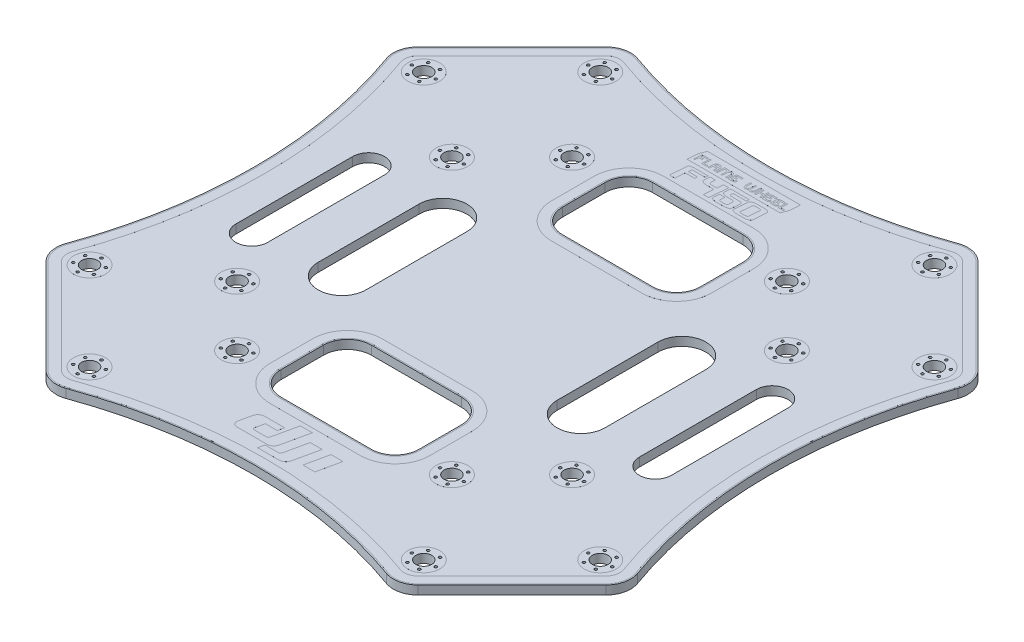
SolidWorks part; units mm, degrees
material "Mounting Plate Material"
ref_plane "Front Plane" through (0, 0, 0) normal (0, 0, 1) x (1, 0, 0)
ref_plane "Top Plane" through (0, 0, 0) normal (0, 1, 0) x (1, 0, 0)
ref_plane "Right Plane" through (0, 0, 0) normal (1, 0, 0) x (0, 0, -1)
sketch "Sketch1" plane through (0, 0, 0) normal (0, 1, 0) x (1, 0, 0)
  line L0 (-48.55, 0) -> (48.55, 0) construction
  line L1 (0, 48.55) -> (0, -48.55) construction
  line L2 (-30.1605, 53.8) -> (30.1605, 53.8) construction
  line L3 (0, 48.55) -> (0, 53.8) construction
  line L4 (-53.8, 30.1605) -> (-53.8, -30.1605) construction
  line L5 (-30.1605, -53.8) -> (30.1605, -53.8) construction
  line L6 (53.8, -30.1605) -> (53.8, 30.1605) construction
  line L7 (35.0464, 52.7056) -> (52.7056, 35.0464)
  line L8 (-52.7056, 35.0464) -> (-35.0464, 52.7056)
  line L9 (-52.7056, -35.0464) -> (-35.0464, -52.7056)
  line L10 (35.0464, -52.7056) -> (52.7056, -35.0464)
  line L11 (-43.876, -43.876) -> (43.876, 43.876) construction
  line L12 (-43.876, 43.876) -> (43.876, -43.876) construction
  line L13 (-31.7403, 54.075) -> (-31.7403, -54.075) construction
  line L14 (-31.7403, -54.075) -> (31.7403, -54.075) construction
  arc A0 (-30.1605, 53.8) -> (30.1605, 53.8) centre (0, 137.8088) ccw
  arc A1 (53.8, 30.1605) -> (53.8, -30.1605) centre (137.8088, 0) ccw
  arc A2 (30.1605, -53.8) -> (-30.1605, -53.8) centre (0, -137.8088) ccw
  arc A3 (-53.8, -30.1605) -> (-53.8, 30.1605) centre (-137.8088, 0) ccw
  arc A4 (-53.8, -30.1605) -> (-52.7056, -35.0464) centre (-49.3995, -31.7403) ccw
  arc A5 (-35.0464, -52.7056) -> (-30.1605, -53.8) centre (-31.7403, -49.3995) ccw
  arc A6 (30.1605, -53.8) -> (35.0464, -52.7056) centre (31.7403, -49.3995) ccw
  arc A7 (52.7056, -35.0464) -> (53.8, -30.1605) centre (49.3995, -31.7403) ccw
  arc A8 (53.8, 30.1605) -> (52.7056, 35.0464) centre (49.3995, 31.7403) ccw
  arc A9 (35.0464, 52.7056) -> (30.1605, 53.8) centre (31.7403, 49.3995) ccw
  arc A10 (-30.1605, 53.8) -> (-35.0464, 52.7056) centre (-31.7403, 49.3995) ccw
  arc A11 (-52.7056, 35.0464) -> (-53.8, 30.1605) centre (-49.3995, 31.7403) ccw
  point P2 (0, 0)
  point P6 (0, 0)
  point P34 (0, 0)
  dimension "D2" = 108.15
  dimension "D4" = 124.1
  dimension "D1" = 97.1
  dimension "D3" = 5.25
  dimension "D5" = 45
extrude "Boss-Extrude1" add sketch "Sketch1" along normal blind 0.825 and the other way blind 0.825
sketch "Sketch2" plane through (0, 0.825, 0) normal (0, 1, 0) x (1, 0, 0)
  line L0 (0, 18) -> (0, -18) construction
  line L1 (0, 35) -> (0, 18) construction
  line L2 (0, -18) -> (0, -35) construction
  line L3 (-13, 26.5) -> (13, 26.5) construction
  line L4 (13, 30.5) -> (13, 22.5)
  line L5 (-13, 30.5) -> (-13, 22.5)
  line L6 (-8.5, 35) -> (8.5, 35)
  line L7 (-8.5, 18) -> (8.5, 18)
  line L8 (-13, -26.5) -> (13, -26.5) construction
  line L9 (-13, -22.5) -> (-13, -30.5)
  line L10 (13, -22.5) -> (13, -30.5)
  line L11 (-8.5, -18) -> (8.5, -18)
  line L12 (-8.5, -35) -> (8.5, -35)
  line L13 (-18, 0) -> (18, 0) construction
  line L14 (-18, 0) -> (-27, 0) construction
  line L15 (18, 0) -> (27, 0) construction
  line L16 (-22.5, 9.5) -> (-22.5, -9.5) construction
  line L17 (22.5, 9.5) -> (22.5, -9.5) construction
  line L18 (-27, -9.5) -> (-27, 9.5)
  line L19 (-18, -9.5) -> (-18, 9.5)
  line L20 (18, -9.5) -> (18, 9.5)
  line L21 (27, -9.5) -> (27, 9.5)
  line L22 (-35, 0) -> (-27, 0) construction
  line L23 (-41, 0) -> (-35, 0) construction
  line L24 (27, 0) -> (35, 0) construction
  line L25 (35, 0) -> (41, 0) construction
  line L26 (-35, 11) -> (-35, -11)
  line L27 (-41, 11) -> (-41, -11)
  line L28 (-38, 11) -> (-38, -11) construction
  line L29 (35, 11) -> (35, -11)
  line L30 (41, 11) -> (41, -11)
  line L31 (38, 11) -> (38, -11) construction
  arc A0 (-8.5, 35) -> (-13, 30.5) centre (-8.5, 30.5) ccw
  arc A1 (13, 30.5) -> (8.5, 35) centre (8.5, 30.5) ccw
  arc A2 (-13, 22.5) -> (-8.5, 18) centre (-8.5, 22.5) ccw
  arc A3 (8.5, 18) -> (13, 22.5) centre (8.5, 22.5) ccw
  arc A4 (-8.5, -18) -> (-13, -22.5) centre (-8.5, -22.5) ccw
  arc A5 (13, -22.5) -> (8.5, -18) centre (8.5, -22.5) ccw
  arc A6 (8.5, -35) -> (13, -30.5) centre (8.5, -30.5) ccw
  arc A7 (-13, -30.5) -> (-8.5, -35) centre (-8.5, -30.5) ccw
  arc A8 (27, 9.5) -> (18, 9.5) centre (22.5, 9.5) ccw
  arc A9 (18, -9.5) -> (27, -9.5) centre (22.5, -9.5) ccw
  arc A10 (-27, -9.5) -> (-18, -9.5) centre (-22.5, -9.5) ccw
  arc A11 (-18, 9.5) -> (-27, 9.5) centre (-22.5, 9.5) ccw
  arc A12 (-35, 11) -> (-41, 11) centre (-38, 11) ccw
  arc A13 (-41, -11) -> (-35, -11) centre (-38, -11) ccw
  arc A14 (41, 11) -> (35, 11) centre (38, 11) ccw
  arc A15 (35, -11) -> (41, -11) centre (38, -11) ccw
  point P5 (0, 26.5)
  point P22 (0, -26.5)
  point P34 (-22.5, 0)
  point P36 (0, 0)
  point P45 (22.5, 0)
  point P64 (-38, 0)
  point P69 (38, 0)
  dimension "D6" = 26
  dimension "D8" = 36
  dimension "D13" = 8
  dimension "D18" = 22
  dimension "D1" = 36
  dimension "D2" = 17
  dimension "D3" = 17
  dimension "D4" = 26
  dimension "D5" = 8
  dimension "D7" = 8
  dimension "D9" = 9
  dimension "D10" = 9
  dimension "D11" = 19
  dimension "D12" = 19
  dimension "D14" = 8
  dimension "D15" = 6
  dimension "D16" = 6
  dimension "D17" = 22
extrude "Cut-Extrude1" cut sketch "Sketch2" against normal up to surface (1.65 mm away) up to face at (0, -0.825, 0)
sketch "Sketch3" plane through (0, 0.825, 0) normal (0, 1, 0) x (1, 0, 0)
  line L0 (-48.0833, -31.4663) -> (-31.4663, -48.0833) construction
  line L1 (-52.7056, -35.0464) -> (-35.0464, -52.7056) construction
  line L2 (-39.7748, -39.7748) -> (-43.876, -43.876) construction
  line L3 (43.876, -43.876) -> (39.7748, -39.7748) construction
  line L4 (31.4663, -48.0833) -> (48.0833, -31.4663) construction
  line L5 (43.876, 43.876) -> (39.7748, 39.7748) construction
  line L6 (31.4663, 48.0833) -> (48.0833, 31.4663) construction
  line L7 (-43.876, 43.876) -> (-39.7748, 39.7748) construction
  line L8 (-31.4663, 48.0833) -> (-48.0833, 31.4663) construction
  line L9 (-35.0464, 52.7056) -> (-52.7056, 35.0464) construction
  line L10 (52.7056, 35.0464) -> (35.0464, 52.7056) construction
  line L11 (35.0464, -52.7056) -> (52.7056, -35.0464) construction
  line L12 (-31.5403, -20.2266) -> (-20.2266, -31.5403) construction
  line L13 (31.5403, -20.2266) -> (20.2266, -31.5403) construction
  line L14 (-31.5403, 20.2266) -> (-20.2266, 31.5403) construction
  line L15 (20.2266, 31.5403) -> (31.5403, 20.2266) construction
  line L16 (-25.8834, -25.8834) -> (-39.7748, -39.7748) construction
  line L17 (-39.7748, 39.7748) -> (-25.8834, 25.8834) construction
  line L18 (39.7748, 39.7748) -> (25.8834, 25.8834) construction
  line L19 (25.8834, -25.8834) -> (39.7748, -39.7748) construction
  line L20 (-20.2266, -31.5403) -> (-31.4663, -48.0833) construction
  line L21 (-31.5403, -20.2266) -> (-48.0833, -31.4663) construction
  circle A0 centre (-48.0833, -31.4663) radius 1.5
  circle A1 centre (-31.4663, -48.0833) radius 1.5
  circle A2 centre (31.4663, -48.0833) radius 1.5
  circle A3 centre (48.0833, -31.4663) radius 1.5
  circle A4 centre (48.0833, 31.4663) radius 1.5
  circle A5 centre (31.4663, 48.0833) radius 1.5
  circle A6 centre (-31.4663, 48.0833) radius 1.5
  circle A7 centre (-48.0833, 31.4663) radius 1.5
  circle A8 centre (-31.5403, -20.2266) radius 1.5
  circle A9 centre (-20.2266, -31.5403) radius 1.5
  circle A10 centre (-31.5403, 20.2266) radius 1.5
  circle A11 centre (-20.2266, 31.5403) radius 1.5
  circle A12 centre (20.2266, 31.5403) radius 1.5
  circle A13 centre (31.5403, 20.2266) radius 1.5
  circle A14 centre (31.5403, -20.2266) radius 1.5
  circle A15 centre (20.2266, -31.5403) radius 1.5
  dimension "D3" = 3
  dimension "D4" = 20
  dimension "D1" = 23.5
  dimension "D2" = 5.8
  dimension "D5" = 16
extrude "Cut-Extrude2" cut sketch "Sketch3" against normal up to surface (1.65 mm away) up to face at (38, -0.825, 0)
sketch "Sketch4" plane through (0, 0.825, 0) normal (0, 1, 0) x (1, 0, 0)
  line L0 (13.25, -30.5) -> (13.25, -22.5)
  line L1 (-13.25, -30.5) -> (-13.25, -22.5)
  line L2 (-8.5, -17.75) -> (8.5, -17.75)
  line L3 (-8.5, -35.25) -> (8.5, -35.25)
  line L4 (13, -30.5) -> (13, -22.5) construction
  line L5 (15.05, -30.5) -> (15.05, -22.5)
  line L6 (-8.5, -15.95) -> (8.5, -15.95)
  line L7 (-15.05, -30.5) -> (-15.05, -22.5)
  line L8 (-8.5, -37.05) -> (8.5, -37.05)
  line L9 (-8.5, 17.75) -> (8.5, 17.75)
  line L10 (-13.25, 22.5) -> (-13.25, 30.5)
  line L11 (-8.5, 35.25) -> (8.5, 35.25)
  line L12 (13.25, 30.5) -> (13.25, 22.5)
  line L13 (13, 22.5) -> (13, 30.5) construction
  line L14 (15.05, 30.5) -> (15.05, 22.5)
  line L15 (-8.5, 15.95) -> (8.5, 15.95)
  line L16 (-15.05, 22.5) -> (-15.05, 30.5)
  line L17 (-8.5, 37.05) -> (8.5, 37.05)
  line L18 (34.8696, -52.5288) -> (52.5288, -34.8696)
  line L19 (35.0464, -52.7056) -> (52.7056, -35.0464) construction
  line L20 (34.8696, 52.5288) -> (52.5288, 34.8696)
  line L21 (52.7056, 35.0464) -> (35.0464, 52.7056) construction
  line L22 (-52.5288, 34.8696) -> (-34.8696, 52.5288)
  line L23 (-35.0464, 52.7056) -> (-52.7056, 35.0464) construction
  line L24 (-52.5288, -34.8696) -> (-34.8696, -52.5288)
  line L25 (-52.7056, -35.0464) -> (-35.0464, -52.7056) construction
  line L26 (-51.256, 33.5968) -> (-33.5968, 51.256)
  line L27 (33.5968, 51.256) -> (51.256, 33.5968)
  line L28 (33.5968, -51.256) -> (51.256, -33.5968)
  line L29 (-51.256, -33.5968) -> (-33.5968, -51.256)
  line L30 (-31.4663, -45.8333) -> (-31.4663, -46.5833) construction
  line L31 (-29.5177, -46.9583) -> (-31.4663, -45.8333) construction
  line L32 (-31.4663, -45.8333) -> (-33.4148, -46.9583) construction
  line L33 (-33.4148, -46.9583) -> (-33.4148, -49.2083) construction
  line L34 (-33.4148, -49.2083) -> (-31.4663, -50.3333) construction
  line L35 (-31.4663, -50.3333) -> (-29.5177, -49.2083) construction
  line L36 (-29.5177, -49.2083) -> (-29.5177, -46.9583) construction
  line L37 (-31.4663, -45.8333) -> (-31.4663, -45.0833) construction
  line L39 (-48.0833, -29.2163) -> (-50.0318, -30.3413) construction
  line L40 (-50.0318, -30.3413) -> (-50.0318, -32.5913) construction
  line L41 (-50.0318, -32.5913) -> (-48.0833, -33.7163) construction
  line L42 (-48.0833, -33.7163) -> (-46.1347, -32.5913) construction
  line L43 (-46.1347, -32.5913) -> (-46.1347, -30.3413) construction
  line L44 (-46.1347, -30.3413) -> (-48.0833, -29.2163) construction
  line L45 (-31.5403, -17.9766) -> (-33.4888, -19.1016) construction
  line L46 (-33.4888, -19.1016) -> (-33.4888, -21.3516) construction
  line L47 (-33.4888, -21.3516) -> (-31.5403, -22.4766) construction
  line L48 (-31.5403, -22.4766) -> (-29.5917, -21.3516) construction
  line L49 (-29.5917, -21.3516) -> (-29.5917, -19.1016) construction
  line L50 (-29.5917, -19.1016) -> (-31.5403, -17.9766) construction
  line L51 (-20.2266, -29.2903) -> (-22.1751, -30.4153) construction
  line L52 (-22.1751, -30.4153) -> (-22.1751, -32.6653) construction
  line L53 (-22.1751, -32.6653) -> (-20.2266, -33.7903) construction
  line L54 (-20.2266, -33.7903) -> (-18.278, -32.6653) construction
  line L55 (-18.278, -32.6653) -> (-18.278, -30.4153) construction
  line L56 (-18.278, -30.4153) -> (-20.2266, -29.2903) construction
  line L57 (20.2266, 33.7903) -> (18.278, 32.6653) construction
  line L58 (18.278, 32.6653) -> (18.278, 30.4153) construction
  line L59 (18.278, 30.4153) -> (20.2266, 29.2903) construction
  line L60 (20.2266, 29.2903) -> (22.1751, 30.4153) construction
  line L61 (22.1751, 30.4153) -> (22.1751, 32.6653) construction
  line L62 (22.1751, 32.6653) -> (20.2266, 33.7903) construction
  line L63 (31.5403, 22.4766) -> (29.5917, 21.3516) construction
  line L64 (29.5917, 21.3516) -> (29.5917, 19.1016) construction
  line L65 (29.5917, 19.1016) -> (31.5403, 17.9766) construction
  line L66 (31.5403, 17.9766) -> (33.4888, 19.1016) construction
  line L67 (33.4888, 19.1016) -> (33.4888, 21.3516) construction
  line L68 (33.4888, 21.3516) -> (31.5403, 22.4766) construction
  line L69 (48.0833, 33.7163) -> (46.1347, 32.5913) construction
  line L70 (46.1347, 32.5913) -> (46.1347, 30.3413) construction
  line L71 (46.1347, 30.3413) -> (48.0833, 29.2163) construction
  line L72 (48.0833, 29.2163) -> (50.0318, 30.3413) construction
  line L73 (50.0318, 30.3413) -> (50.0318, 32.5913) construction
  line L74 (50.0318, 32.5913) -> (48.0833, 33.7163) construction
  line L75 (31.4663, 50.3333) -> (29.5177, 49.2083) construction
  line L76 (29.5177, 49.2083) -> (29.5177, 46.9583) construction
  line L77 (29.5177, 46.9583) -> (31.4663, 45.8333) construction
  line L78 (31.4663, 45.8333) -> (33.4148, 46.9583) construction
  line L79 (33.4148, 46.9583) -> (33.4148, 49.2083) construction
  line L80 (33.4148, 49.2083) -> (31.4663, 50.3333) construction
  line L81 (-50.3333, 31.4663) -> (-49.2083, 29.5177) construction
  line L82 (-49.2083, 29.5177) -> (-46.9583, 29.5177) construction
  line L83 (-46.9583, 29.5177) -> (-45.8333, 31.4663) construction
  line L84 (-45.8333, 31.4663) -> (-46.9583, 33.4148) construction
  line L85 (-46.9583, 33.4148) -> (-49.2083, 33.4148) construction
  line L86 (-49.2083, 33.4148) -> (-50.3333, 31.4663) construction
  line L87 (-33.7903, 20.2266) -> (-32.6653, 18.278) construction
  line L88 (-32.6653, 18.278) -> (-30.4153, 18.278) construction
  line L89 (-30.4153, 18.278) -> (-29.2903, 20.2266) construction
  line L90 (-29.2903, 20.2266) -> (-30.4153, 22.1751) construction
  line L91 (-30.4153, 22.1751) -> (-32.6653, 22.1751) construction
  line L92 (-32.6653, 22.1751) -> (-33.7903, 20.2266) construction
  line L93 (-22.4766, 31.5403) -> (-21.3516, 29.5917) construction
  line L94 (-21.3516, 29.5917) -> (-19.1016, 29.5917) construction
  line L95 (-19.1016, 29.5917) -> (-17.9766, 31.5403) construction
  line L96 (-17.9766, 31.5403) -> (-19.1016, 33.4888) construction
  line L97 (-19.1016, 33.4888) -> (-21.3516, 33.4888) construction
  line L98 (-21.3516, 33.4888) -> (-22.4766, 31.5403) construction
  line L99 (-29.2163, 48.0833) -> (-30.3413, 50.0318) construction
  line L100 (-30.3413, 50.0318) -> (-32.5913, 50.0318) construction
  line L101 (-32.5913, 50.0318) -> (-33.7163, 48.0833) construction
  line L102 (-33.7163, 48.0833) -> (-32.5913, 46.1347) construction
  line L103 (-32.5913, 46.1347) -> (-30.3413, 46.1347) construction
  line L104 (-30.3413, 46.1347) -> (-29.2163, 48.0833) construction
  line L105 (22.4766, -31.5403) -> (21.3516, -29.5917) construction
  line L106 (21.3516, -29.5917) -> (19.1016, -29.5917) construction
  line L107 (19.1016, -29.5917) -> (17.9766, -31.5403) construction
  line L108 (17.9766, -31.5403) -> (19.1016, -33.4888) construction
  line L109 (19.1016, -33.4888) -> (21.3516, -33.4888) construction
  line L110 (21.3516, -33.4888) -> (22.4766, -31.5403) construction
  line L111 (33.7903, -20.2266) -> (32.6653, -18.278) construction
  line L112 (32.6653, -18.278) -> (30.4153, -18.278) construction
  line L113 (30.4153, -18.278) -> (29.2903, -20.2266) construction
  line L114 (29.2903, -20.2266) -> (30.4153, -22.1751) construction
  line L115 (30.4153, -22.1751) -> (32.6653, -22.1751) construction
  line L116 (32.6653, -22.1751) -> (33.7903, -20.2266) construction
  line L117 (33.7163, -48.0833) -> (32.5913, -46.1347) construction
  line L118 (32.5913, -46.1347) -> (30.3413, -46.1347) construction
  line L119 (30.3413, -46.1347) -> (29.2163, -48.0833) construction
  line L120 (29.2163, -48.0833) -> (30.3413, -50.0318) construction
  line L121 (30.3413, -50.0318) -> (32.5913, -50.0318) construction
  line L122 (32.5913, -50.0318) -> (33.7163, -48.0833) construction
  line L123 (50.3333, -31.4663) -> (49.2083, -29.5177) construction
  line L124 (49.2083, -29.5177) -> (46.9583, -29.5177) construction
  line L125 (46.9583, -29.5177) -> (45.8333, -31.4663) construction
  line L126 (45.8333, -31.4663) -> (46.9583, -33.4148) construction
  line L127 (46.9583, -33.4148) -> (49.2083, -33.4148) construction
  line L128 (49.2083, -33.4148) -> (50.3333, -31.4663) construction
  arc A0 (-8.5, -17.75) -> (-13.25, -22.5) centre (-8.5, -22.5) ccw
  arc A1 (13.25, -22.5) -> (8.5, -17.75) centre (8.5, -22.5) ccw
  arc A2 (-13.25, -30.5) -> (-8.5, -35.25) centre (-8.5, -30.5) ccw
  arc A3 (8.5, -35.25) -> (13.25, -30.5) centre (8.5, -30.5) ccw
  arc A4 (8.5, -35) -> (13, -30.5) centre (8.5, -30.5) ccw construction
  arc A5 (13, -22.5) -> (8.5, -18) centre (8.5, -22.5) ccw construction
  arc A6 (-8.5, -18) -> (-13, -22.5) centre (-8.5, -22.5) ccw construction
  arc A7 (-13, -30.5) -> (-8.5, -35) centre (-8.5, -30.5) ccw construction
  arc A8 (15.05, -22.5) -> (8.5, -15.95) centre (8.5, -22.5) ccw
  arc A9 (-8.5, -15.95) -> (-15.05, -22.5) centre (-8.5, -22.5) ccw
  arc A10 (-15.05, -30.5) -> (-8.5, -37.05) centre (-8.5, -30.5) ccw
  arc A11 (8.5, -37.05) -> (15.05, -30.5) centre (8.5, -30.5) ccw
  arc A12 (-13.25, 22.5) -> (-8.5, 17.75) centre (-8.5, 22.5) ccw
  arc A13 (-8.5, 35.25) -> (-13.25, 30.5) centre (-8.5, 30.5) ccw
  arc A14 (13.25, 30.5) -> (8.5, 35.25) centre (8.5, 30.5) ccw
  arc A15 (8.5, 17.75) -> (13.25, 22.5) centre (8.5, 22.5) ccw
  arc A16 (8.5, 18) -> (13, 22.5) centre (8.5, 22.5) ccw construction
  arc A17 (13, 30.5) -> (8.5, 35) centre (8.5, 30.5) ccw construction
  arc A18 (-8.5, 35) -> (-13, 30.5) centre (-8.5, 30.5) ccw construction
  arc A19 (-13, 22.5) -> (-8.5, 18) centre (-8.5, 22.5) ccw construction
  arc A20 (8.5, 15.95) -> (15.05, 22.5) centre (8.5, 22.5) ccw
  arc A21 (-15.05, 22.5) -> (-8.5, 15.95) centre (-8.5, 22.5) ccw
  arc A22 (-8.5, 37.05) -> (-15.05, 30.5) centre (-8.5, 30.5) ccw
  arc A23 (15.05, 30.5) -> (8.5, 37.05) centre (8.5, 30.5) ccw
  arc A24 (30.245, -53.5647) -> (-30.245, -53.5647) centre (0, -137.8088) ccw
  arc A25 (30.1605, -53.8) -> (-30.1605, -53.8) centre (0, -137.8088) ccw construction
  arc A26 (-53.5647, -30.245) -> (-53.5647, 30.245) centre (-137.8088, 0) ccw
  arc A27 (-30.245, 53.5647) -> (30.245, 53.5647) centre (0, 137.8088) ccw
  arc A28 (53.5647, 30.245) -> (53.5647, -30.245) centre (137.8088, 0) ccw
  arc A29 (53.8, 30.1605) -> (53.8, -30.1605) centre (137.8088, 0) ccw construction
  arc A30 (-30.1605, 53.8) -> (30.1605, 53.8) centre (0, 137.8088) ccw construction
  arc A31 (-53.8, -30.1605) -> (-53.8, 30.1605) centre (-137.8088, 0) ccw construction
  arc A32 (34.8696, 52.5288) -> (30.245, 53.5647) centre (31.7403, 49.3995) ccw
  arc A33 (35.0464, 52.7056) -> (30.1605, 53.8) centre (31.7403, 49.3995) ccw construction
  arc A34 (53.5647, 30.245) -> (52.5288, 34.8696) centre (49.3995, 31.7403) ccw
  arc A35 (53.8, 30.1605) -> (52.7056, 35.0464) centre (49.3995, 31.7403) ccw construction
  arc A36 (52.5288, -34.8696) -> (53.5647, -30.245) centre (49.3995, -31.7403) ccw
  arc A37 (52.7056, -35.0464) -> (53.8, -30.1605) centre (49.3995, -31.7403) ccw construction
  arc A38 (30.245, -53.5647) -> (34.8696, -52.5288) centre (31.7403, -49.3995) ccw
  arc A39 (30.1605, -53.8) -> (35.0464, -52.7056) centre (31.7403, -49.3995) ccw construction
  arc A40 (-34.8696, -52.5288) -> (-30.245, -53.5647) centre (-31.7403, -49.3995) ccw
  arc A41 (-35.0464, -52.7056) -> (-30.1605, -53.8) centre (-31.7403, -49.3995) ccw construction
  arc A42 (-53.5647, -30.245) -> (-52.5288, -34.8696) centre (-49.3995, -31.7403) ccw
  arc A43 (-53.8, -30.1605) -> (-52.7056, -35.0464) centre (-49.3995, -31.7403) ccw construction
  arc A44 (-52.5288, 34.8696) -> (-53.5647, 30.245) centre (-49.3995, 31.7403) ccw
  arc A45 (-52.7056, 35.0464) -> (-53.8, 30.1605) centre (-49.3995, 31.7403) ccw construction
  arc A46 (-30.245, 53.5647) -> (-34.8696, 52.5288) centre (-31.7403, 49.3995) ccw
  arc A47 (-30.1605, 53.8) -> (-35.0464, 52.7056) centre (-31.7403, 49.3995) ccw construction
  arc A48 (-51.8706, -30.8532) -> (-51.8706, 30.8532) centre (-137.8088, 0) ccw
  arc A49 (-51.256, 33.5968) -> (-51.8706, 30.8532) centre (-49.3995, 31.7403) ccw
  arc A50 (-30.8532, 51.8706) -> (-33.5968, 51.256) centre (-31.7403, 49.3995) ccw
  arc A51 (-30.8532, 51.8706) -> (30.8532, 51.8706) centre (0, 137.8088) ccw
  arc A52 (33.5968, 51.256) -> (30.8532, 51.8706) centre (31.7403, 49.3995) ccw
  arc A53 (51.8706, 30.8532) -> (51.256, 33.5968) centre (49.3995, 31.7403) ccw
  arc A54 (51.8706, 30.8532) -> (51.8706, -30.8532) centre (137.8088, 0) ccw
  arc A55 (51.256, -33.5968) -> (51.8706, -30.8532) centre (49.3995, -31.7403) ccw
  arc A56 (30.8532, -51.8706) -> (33.5968, -51.256) centre (31.7403, -49.3995) ccw
  arc A57 (30.8532, -51.8706) -> (-30.8532, -51.8706) centre (0, -137.8088) ccw
  arc A58 (-33.5968, -51.256) -> (-30.8532, -51.8706) centre (-31.7403, -49.3995) ccw
  arc A59 (-51.8706, -30.8532) -> (-51.256, -33.5968) centre (-49.3995, -31.7403) ccw
  circle A60 centre (-31.4663, -48.0833) radius 3
  circle A61 centre (-48.0833, -31.4663) radius 3
  circle A62 centre (-31.5403, -20.2266) radius 3
  circle A63 centre (-20.2266, -31.5403) radius 3
  circle A64 centre (-48.0833, 31.4663) radius 3
  circle A65 centre (-31.5403, 20.2266) radius 3
  circle A66 centre (-20.2266, 31.5403) radius 3
  circle A67 centre (-31.4663, 48.0833) radius 3
  circle A68 centre (20.2266, 31.5403) radius 3
  circle A69 centre (31.4663, 48.0833) radius 3
  circle A70 centre (48.0833, 31.4663) radius 3
  circle A71 centre (31.5403, 20.2266) radius 3
  circle A72 centre (20.2266, -31.5403) radius 3
  circle A73 centre (31.5403, -20.2266) radius 3
  circle A74 centre (48.0833, -31.4663) radius 3
  circle A75 centre (31.4663, -48.0833) radius 3
  circle A76 centre (-31.4663, -48.0833) radius 1.5 construction
  circle A77 centre (-48.0833, -31.4663) radius 1.5 construction
  circle A78 centre (-31.5403, -20.2266) radius 1.5 construction
  circle A79 centre (-20.2266, -31.5403) radius 1.5 construction
  circle A80 centre (20.2266, -31.5403) radius 1.5 construction
  circle A81 centre (31.4663, -48.0833) radius 1.5 construction
  circle A82 centre (48.0833, -31.4663) radius 1.5 construction
  circle A83 centre (31.5403, -20.2266) radius 1.5 construction
  circle A84 centre (48.0833, 31.4663) radius 1.5 construction
  circle A85 centre (31.5403, 20.2266) radius 1.5 construction
  circle A86 centre (20.2266, 31.5403) radius 1.5 construction
  circle A87 centre (31.4663, 48.0833) radius 1.5 construction
  circle A88 centre (-20.2266, 31.5403) radius 1.5 construction
  circle A89 centre (-31.5403, 20.2266) radius 1.5 construction
  circle A90 centre (-48.0833, 31.4663) radius 1.5 construction
  circle A91 centre (-31.4663, 48.0833) radius 1.5 construction
  circle A92 centre (-48.0833, -31.4663) radius 1.5
  circle A93 centre (-31.4663, -48.0833) radius 1.5
  circle A94 centre (-20.2266, -31.5403) radius 1.5
  circle A95 centre (-31.5403, -20.2266) radius 1.5
  circle A96 centre (-48.0833, 31.4663) radius 1.5
  circle A97 centre (-31.5403, 20.2266) radius 1.5
  circle A98 centre (-20.2266, 31.5403) radius 1.5
  circle A99 centre (-31.4663, 48.0833) radius 1.5
  circle A100 centre (20.2266, 31.5403) radius 1.5
  circle A101 centre (31.4663, 48.0833) radius 1.5
  circle A102 centre (48.0833, 31.4663) radius 1.5
  circle A103 centre (31.5403, 20.2266) radius 1.5
  circle A104 centre (31.5403, -20.2266) radius 1.5
  circle A105 centre (20.2266, -31.5403) radius 1.5
  circle A106 centre (48.0833, -31.4663) radius 1.5
  circle A107 centre (31.4663, -48.0833) radius 1.5
  circle A108 centre (-31.4663, -48.0833) radius 1.9486 construction
  circle A109 centre (-48.0833, -31.4663) radius 1.9486 construction
  circle A110 centre (-31.5403, -20.2266) radius 1.9486 construction
  circle A111 centre (-20.2266, -31.5403) radius 1.9486 construction
  circle A112 centre (-31.4663, -50.3333) radius 0.25
  circle A113 centre (-29.5177, -49.2083) radius 0.25
  circle A114 centre (-29.5177, -46.9583) radius 0.25
  circle A115 centre (-31.4663, -45.8333) radius 0.25
  circle A116 centre (-33.4148, -46.9583) radius 0.25
  circle A117 centre (-33.4148, -49.2083) radius 0.25
  circle A118 centre (-48.0833, -33.7163) radius 0.25
  circle A119 centre (-46.1347, -32.5913) radius 0.25
  circle A120 centre (-46.1347, -30.3413) radius 0.25
  circle A121 centre (-48.0833, -29.2163) radius 0.25
  circle A122 centre (-50.0318, -30.3413) radius 0.25
  circle A123 centre (-50.0318, -32.5913) radius 0.25
  circle A124 centre (-31.5403, -22.4766) radius 0.25
  circle A125 centre (-29.5917, -21.3516) radius 0.25
  circle A126 centre (-29.5917, -19.1016) radius 0.25
  circle A127 centre (-31.5403, -17.9766) radius 0.25
  circle A128 centre (-33.4888, -19.1016) radius 0.25
  circle A129 centre (-33.4888, -21.3516) radius 0.25
  circle A130 centre (-20.2266, -33.7903) radius 0.25
  circle A131 centre (-18.278, -32.6653) radius 0.25
  circle A132 centre (-18.278, -30.4153) radius 0.25
  circle A133 centre (-20.2266, -29.2903) radius 0.25
  circle A134 centre (-22.1751, -30.4153) radius 0.25
  circle A135 centre (-22.1751, -32.6653) radius 0.25
  circle A136 centre (20.2266, 31.5403) radius 1.9486 construction
  circle A137 centre (31.5403, 20.2266) radius 1.9486 construction
  circle A138 centre (48.0833, 31.4663) radius 1.9486 construction
  circle A139 centre (31.4663, 48.0833) radius 1.9486 construction
  circle A140 centre (20.2266, 29.2903) radius 0.25
  circle A141 centre (22.1751, 30.4153) radius 0.25
  circle A142 centre (22.1751, 32.6653) radius 0.25
  circle A143 centre (18.278, 30.4153) radius 0.25
  circle A144 centre (18.278, 32.6653) radius 0.25
  circle A145 centre (20.2266, 33.7903) radius 0.25
  circle A146 centre (31.4663, 45.8333) radius 0.25
  circle A147 centre (29.5177, 46.9583) radius 0.25
  circle A148 centre (29.5177, 49.2083) radius 0.25
  circle A149 centre (31.4663, 50.3333) radius 0.25
  circle A150 centre (33.4148, 49.2083) radius 0.25
  circle A151 centre (33.4148, 46.9583) radius 0.25
  circle A152 centre (29.5917, 21.3516) radius 0.25
  circle A153 centre (29.5917, 19.1016) radius 0.25
  circle A154 centre (31.5403, 17.9766) radius 0.25
  circle A155 centre (33.4888, 19.1016) radius 0.25
  circle A156 centre (33.4888, 21.3516) radius 0.25
  circle A157 centre (31.5403, 22.4766) radius 0.25
  circle A158 centre (48.0833, 29.2163) radius 0.25
  circle A159 centre (46.1347, 30.3413) radius 0.25
  circle A160 centre (50.0318, 30.3413) radius 0.25
  circle A161 centre (50.0318, 32.5913) radius 0.25
  circle A162 centre (48.0833, 33.7163) radius 0.25
  circle A163 centre (46.1347, 32.5913) radius 0.25
  circle A164 centre (-48.0833, 31.4663) radius 1.9486 construction
  circle A165 centre (-31.5403, 20.2266) radius 1.9486 construction
  circle A166 centre (-20.2266, 31.5403) radius 1.9486 construction
  circle A167 centre (-31.4663, 48.0833) radius 1.9486 construction
  circle A168 centre (-46.9583, 29.5177) radius 0.25
  circle A169 centre (-45.8333, 31.4663) radius 0.25
  circle A170 centre (-46.9583, 33.4148) radius 0.25
  circle A171 centre (-49.2083, 33.4148) radius 0.25
  circle A172 centre (-50.3333, 31.4663) radius 0.25
  circle A173 centre (-49.2083, 29.5177) radius 0.25
  circle A174 centre (-32.6653, 18.278) radius 0.25
  circle A175 centre (-33.7903, 20.2266) radius 0.25
  circle A176 centre (-32.6653, 22.1751) radius 0.25
  circle A177 centre (-30.4153, 22.1751) radius 0.25
  circle A178 centre (-29.2903, 20.2266) radius 0.25
  circle A179 centre (-30.4153, 18.278) radius 0.25
  circle A180 centre (-19.1016, 29.5917) radius 0.25
  circle A181 centre (-21.3516, 29.5917) radius 0.25
  circle A182 centre (-22.4766, 31.5403) radius 0.25
  circle A183 centre (-21.3516, 33.4888) radius 0.25
  circle A184 centre (-19.1016, 33.4888) radius 0.25
  circle A185 centre (-17.9766, 31.5403) radius 0.25
  circle A186 centre (-32.5913, 46.1347) radius 0.25
  circle A187 centre (-33.7163, 48.0833) radius 0.25
  circle A188 centre (-32.5913, 50.0318) radius 0.25
  circle A189 centre (-30.3413, 50.0318) radius 0.25
  circle A190 centre (-29.2163, 48.0833) radius 0.25
  circle A191 centre (-30.3413, 46.1347) radius 0.25
  circle A192 centre (20.2266, -31.5403) radius 1.9486 construction
  circle A193 centre (31.5403, -20.2266) radius 1.9486 construction
  circle A194 centre (31.4663, -48.0833) radius 1.9486 construction
  circle A195 centre (48.0833, -31.4663) radius 1.9486 construction
  circle A196 centre (19.1016, -33.4888) radius 0.25
  circle A197 centre (21.3516, -33.4888) radius 0.25
  circle A198 centre (22.4766, -31.5403) radius 0.25
  circle A199 centre (21.3516, -29.5917) radius 0.25
  circle A200 centre (19.1016, -29.5917) radius 0.25
  circle A201 centre (17.9766, -31.5403) radius 0.25
  circle A202 centre (30.3413, -50.0318) radius 0.25
  circle A203 centre (29.2163, -48.0833) radius 0.25
  circle A204 centre (30.3413, -46.1347) radius 0.25
  circle A205 centre (32.5913, -46.1347) radius 0.25
  circle A206 centre (33.7163, -48.0833) radius 0.25
  circle A207 centre (32.5913, -50.0318) radius 0.25
  circle A208 centre (46.9583, -33.4148) radius 0.25
  circle A209 centre (45.8333, -31.4663) radius 0.25
  circle A210 centre (46.9583, -29.5177) radius 0.25
  circle A211 centre (49.2083, -29.5177) radius 0.25
  circle A212 centre (50.3333, -31.4663) radius 0.25
  circle A213 centre (49.2083, -33.4148) radius 0.25
  circle A214 centre (30.4153, -22.1751) radius 0.25
  circle A215 centre (29.2903, -20.2266) radius 0.25
  circle A216 centre (30.4153, -18.278) radius 0.25
  circle A217 centre (32.6653, -18.278) radius 0.25
  circle A218 centre (33.7903, -20.2266) radius 0.25
  circle A219 centre (32.6653, -22.1751) radius 0.25
  dimension "D1" = 0.25
  dimension "D3" = 0.25
  dimension "D5" = 0.25
  dimension "D7" = 6
  dimension "D8" = 0.5
  dimension "D2" = 1.8
  dimension "D4" = 1.8
  dimension "D6" = 1.8
extrude "Boss-Extrude2" add sketch "Sketch4" along normal blind 0.001 contours A27 A46 L22 A44 A26 A42 L24 A40 A24 A38 L18 A36 A28 A34 L20 A32 A59 A48 A49 L26 A50 A51 A52 L27 A53 A54 A55 L28 A56 A57 A58 L29 | L8 A11 L5 A8 L6 A9 L7 A10 A3 L3 A2 L1 A0 L2 A1 L0 | L14 A23 L17 A22 L16 A21 L15 A20 A15 L9 A12 L10 A13 L11 A14 L12 | A61 A92 | A60 A93 | A63 A94 | A62 A95 | A75 A107 | A72 A105 | A73 A104 | A74 A106 | A71 A103 | A70 A102 | A68 A100 | A69 A101 | A64 A96 | A65 A97 | A66 A98 | A67 A99 region at (12.8716, 0.825, 34.8716) region at (14.6824, 0.825, -26.5) region at (32.3749, 0.825, 52.2324) region at (-34.3814, 0.825, 48.0833) region at (-50.9984, 0.825, 31.4663) region at (-34.4554, 0.825, 20.2266) region at (-23.1417, 0.825, 31.5403) region at (-50.9984, 0.825, -31.4663) region at (-34.4554, 0.825, -20.2266) region at (-23.1417, 0.825, -31.5403) region at (-34.3814, 0.825, -48.0833) region at (17.3114, 0.825, -31.5403) region at (28.5511, 0.825, -48.0833) region at (45.1681, 0.825, -31.4663) region at (28.6251, 0.825, -20.2266) region at (17.3114, 0.825, 31.5403) region at (28.6251, 0.825, 20.2266) region at (45.1681, 0.825, 31.4663) region at (28.5511, 0.825, 48.0833)
mirror "Mirror2" about plane through (0, 0, 0) normal (0, 1, 0) of "Boss-Extrude2"
sketch "Sketch5" plane through (0, 0.825, 0) normal (0, 1, 0) x (1, 0, 0)
  circle A0 centre (-31.4663, -45.8333) radius 0.25
  circle A1 centre (-29.5177, -46.9583) radius 0.25
  circle A2 centre (-29.5177, -49.2083) radius 0.25
  circle A3 centre (-31.4663, -50.3333) radius 0.25
  circle A4 centre (-33.4148, -49.2083) radius 0.25
  circle A5 centre (-33.4148, -46.9583) radius 0.25
  circle A6 centre (-48.0833, -33.7163) radius 0.25
  circle A7 centre (-50.0318, -32.5913) radius 0.25
  circle A8 centre (-50.0318, -30.3413) radius 0.25
  circle A9 centre (-48.0833, -29.2163) radius 0.25
  circle A10 centre (-46.1347, -30.3413) radius 0.25
  circle A11 centre (-46.1347, -32.5913) radius 0.25
  circle A12 centre (-33.4888, -21.3516) radius 0.25
  circle A13 centre (-33.4888, -19.1016) radius 0.25
  circle A14 centre (-31.5403, -17.9766) radius 0.25
  circle A15 centre (-29.5917, -19.1016) radius 0.25
  circle A16 centre (-29.5917, -21.3516) radius 0.25
  circle A17 centre (-31.5403, -22.4766) radius 0.25
  circle A18 centre (-22.1751, -30.4153) radius 0.25
  circle A19 centre (-22.1751, -32.6653) radius 0.25
  circle A20 centre (-20.2266, -33.7903) radius 0.25
  circle A21 centre (-18.278, -32.6653) radius 0.25
  circle A22 centre (-18.278, -30.4153) radius 0.25
  circle A23 centre (-20.2266, -29.2903) radius 0.25
  circle A24 centre (-31.4663, -50.3333) radius 0.25 construction
  circle A25 centre (-33.4148, -49.2083) radius 0.25 construction
  circle A26 centre (-33.4148, -46.9583) radius 0.25 construction
  circle A27 centre (-31.4663, -45.8333) radius 0.25 construction
  circle A28 centre (-29.5177, -46.9583) radius 0.25 construction
  circle A29 centre (-29.5177, -49.2083) radius 0.25 construction
  circle A30 centre (-48.0833, -33.7163) radius 0.25 construction
  circle A31 centre (-50.0318, -32.5913) radius 0.25 construction
  circle A32 centre (-50.0318, -30.3413) radius 0.25 construction
  circle A33 centre (-48.0833, -29.2163) radius 0.25 construction
  circle A34 centre (-46.1347, -30.3413) radius 0.25 construction
  circle A35 centre (-46.1347, -32.5913) radius 0.25 construction
  circle A36 centre (-31.5403, -22.4766) radius 0.25 construction
  circle A37 centre (-33.4888, -21.3516) radius 0.25 construction
  circle A38 centre (-33.4888, -19.1016) radius 0.25 construction
  circle A39 centre (-31.5403, -17.9766) radius 0.25 construction
  circle A40 centre (-29.5917, -19.1016) radius 0.25 construction
  circle A41 centre (-29.5917, -21.3516) radius 0.25 construction
  circle A42 centre (-22.1751, -32.6653) radius 0.25 construction
  circle A43 centre (-22.1751, -30.4153) radius 0.25 construction
  circle A44 centre (-20.2266, -29.2903) radius 0.25 construction
  circle A45 centre (-18.278, -30.4153) radius 0.25 construction
  circle A46 centre (-18.278, -32.6653) radius 0.25 construction
  circle A47 centre (-20.2266, -33.7903) radius 0.25 construction
  circle A48 centre (19.1016, -33.4888) radius 0.25
  circle A49 centre (17.9766, -31.5403) radius 0.25
  circle A50 centre (19.1016, -29.5917) radius 0.25
  circle A51 centre (21.3516, -29.5917) radius 0.25
  circle A52 centre (22.4766, -31.5403) radius 0.25
  circle A53 centre (21.3516, -33.4888) radius 0.25
  circle A54 centre (19.1016, -33.4888) radius 0.25 construction
  circle A55 centre (21.3516, -33.4888) radius 0.25 construction
  circle A56 centre (17.9766, -31.5403) radius 0.25 construction
  circle A57 centre (19.1016, -29.5917) radius 0.25 construction
  circle A58 centre (21.3516, -29.5917) radius 0.25 construction
  circle A59 centre (22.4766, -31.5403) radius 0.25 construction
  circle A60 centre (29.2903, -20.2266) radius 0.25
  circle A61 centre (30.4153, -18.278) radius 0.25
  circle A62 centre (32.6653, -18.278) radius 0.25
  circle A63 centre (30.4153, -22.1751) radius 0.25
  circle A64 centre (32.6653, -22.1751) radius 0.25
  circle A65 centre (33.7903, -20.2266) radius 0.25
  circle A66 centre (29.2903, -20.2266) radius 0.25 construction
  circle A67 centre (30.4153, -18.278) radius 0.25 construction
  circle A68 centre (32.6653, -18.278) radius 0.25 construction
  circle A69 centre (30.4153, -22.1751) radius 0.25 construction
  circle A70 centre (32.6653, -22.1751) radius 0.25 construction
  circle A71 centre (33.7903, -20.2266) radius 0.25 construction
  circle A72 centre (46.9583, -29.5177) radius 0.25
  circle A73 centre (49.2083, -29.5177) radius 0.25
  circle A74 centre (45.8333, -31.4663) radius 0.25
  circle A75 centre (46.9583, -33.4148) radius 0.25
  circle A76 centre (49.2083, -33.4148) radius 0.25
  circle A77 centre (50.3333, -31.4663) radius 0.25
  circle A78 centre (45.8333, -31.4663) radius 0.25 construction
  circle A79 centre (46.9583, -29.5177) radius 0.25 construction
  circle A80 centre (49.2083, -29.5177) radius 0.25 construction
  circle A81 centre (50.3333, -31.4663) radius 0.25 construction
  circle A82 centre (49.2083, -33.4148) radius 0.25 construction
  circle A83 centre (46.9583, -33.4148) radius 0.25 construction
  circle A84 centre (30.3413, -46.1347) radius 0.25
  circle A85 centre (32.5913, -46.1347) radius 0.25
  circle A86 centre (29.2163, -48.0833) radius 0.25
  circle A87 centre (30.3413, -50.0318) radius 0.25
  circle A88 centre (32.5913, -50.0318) radius 0.25
  circle A89 centre (33.7163, -48.0833) radius 0.25
  circle A90 centre (29.2163, -48.0833) radius 0.25 construction
  circle A91 centre (30.3413, -46.1347) radius 0.25 construction
  circle A92 centre (32.5913, -46.1347) radius 0.25 construction
  circle A93 centre (30.3413, -50.0318) radius 0.25 construction
  circle A94 centre (32.5913, -50.0318) radius 0.25 construction
  circle A95 centre (33.7163, -48.0833) radius 0.25 construction
  circle A96 centre (-32.6653, 18.278) radius 0.25
  circle A97 centre (-33.7903, 20.2266) radius 0.25
  circle A98 centre (-32.6653, 22.1751) radius 0.25
  circle A99 centre (-30.4153, 22.1751) radius 0.25
  circle A100 centre (-29.2903, 20.2266) radius 0.25
  circle A101 centre (-30.4153, 18.278) radius 0.25
  circle A102 centre (-32.6653, 18.278) radius 0.25 construction
  circle A103 centre (-33.7903, 20.2266) radius 0.25 construction
  circle A104 centre (-32.6653, 22.1751) radius 0.25 construction
  circle A105 centre (-30.4153, 22.1751) radius 0.25 construction
  circle A106 centre (-29.2903, 20.2266) radius 0.25 construction
  circle A107 centre (-30.4153, 18.278) radius 0.25 construction
  circle A108 centre (-49.2083, 29.5177) radius 0.25
  circle A109 centre (-50.3333, 31.4663) radius 0.25
  circle A110 centre (-49.2083, 33.4148) radius 0.25
  circle A111 centre (-46.9583, 33.4148) radius 0.25
  circle A112 centre (-45.8333, 31.4663) radius 0.25
  circle A113 centre (-46.9583, 29.5177) radius 0.25
  circle A114 centre (-49.2083, 29.5177) radius 0.25 construction
  circle A115 centre (-50.3333, 31.4663) radius 0.25 construction
  circle A116 centre (-49.2083, 33.4148) radius 0.25 construction
  circle A117 centre (-46.9583, 33.4148) radius 0.25 construction
  circle A118 centre (-45.8333, 31.4663) radius 0.25 construction
  circle A119 centre (-46.9583, 29.5177) radius 0.25 construction
  circle A120 centre (-32.5913, 46.1347) radius 0.25
  circle A121 centre (-33.7163, 48.0833) radius 0.25
  circle A122 centre (-32.5913, 50.0318) radius 0.25
  circle A123 centre (-30.3413, 50.0318) radius 0.25
  circle A124 centre (-29.2163, 48.0833) radius 0.25
  circle A125 centre (-30.3413, 46.1347) radius 0.25
  circle A126 centre (-32.5913, 46.1347) radius 0.25 construction
  circle A127 centre (-33.7163, 48.0833) radius 0.25 construction
  circle A128 centre (-32.5913, 50.0318) radius 0.25 construction
  circle A129 centre (-30.3413, 50.0318) radius 0.25 construction
  circle A130 centre (-29.2163, 48.0833) radius 0.25 construction
  circle A131 centre (-30.3413, 46.1347) radius 0.25 construction
  circle A132 centre (-21.3516, 29.5917) radius 0.25
  circle A133 centre (-22.4766, 31.5403) radius 0.25
  circle A134 centre (-21.3516, 33.4888) radius 0.25
  circle A135 centre (-19.1016, 33.4888) radius 0.25
  circle A136 centre (-17.9766, 31.5403) radius 0.25
  circle A137 centre (-19.1016, 29.5917) radius 0.25
  circle A138 centre (-21.3516, 29.5917) radius 0.25 construction
  circle A139 centre (-22.4766, 31.5403) radius 0.25 construction
  circle A140 centre (-21.3516, 33.4888) radius 0.25 construction
  circle A141 centre (-19.1016, 33.4888) radius 0.25 construction
  circle A142 centre (-17.9766, 31.5403) radius 0.25 construction
  circle A143 centre (-19.1016, 29.5917) radius 0.25 construction
  circle A144 centre (20.2266, 29.2903) radius 0.25
  circle A145 centre (18.278, 30.4153) radius 0.25
  circle A146 centre (18.278, 32.6653) radius 0.25
  circle A147 centre (20.2266, 33.7903) radius 0.25
  circle A148 centre (22.1751, 32.6653) radius 0.25
  circle A149 centre (22.1751, 30.4153) radius 0.25
  circle A150 centre (20.2266, 29.2903) radius 0.25 construction
  circle A151 centre (18.278, 30.4153) radius 0.25 construction
  circle A152 centre (18.278, 32.6653) radius 0.25 construction
  circle A153 centre (20.2266, 33.7903) radius 0.25 construction
  circle A154 centre (22.1751, 32.6653) radius 0.25 construction
  circle A155 centre (22.1751, 30.4153) radius 0.25 construction
  circle A156 centre (29.5917, 21.3516) radius 0.25
  circle A157 centre (31.5403, 22.4766) radius 0.25
  circle A158 centre (29.5917, 19.1016) radius 0.25
  circle A159 centre (31.5403, 17.9766) radius 0.25
  circle A160 centre (33.4888, 19.1016) radius 0.25
  circle A161 centre (33.4888, 21.3516) radius 0.25
  circle A162 centre (29.5917, 21.3516) radius 0.25 construction
  circle A163 centre (29.5917, 19.1016) radius 0.25 construction
  circle A164 centre (31.5403, 22.4766) radius 0.25 construction
  circle A165 centre (31.5403, 17.9766) radius 0.25 construction
  circle A166 centre (33.4888, 19.1016) radius 0.25 construction
  circle A167 centre (33.4888, 21.3516) radius 0.25 construction
  circle A168 centre (48.0833, 29.2163) radius 0.25
  circle A169 centre (50.0318, 30.3413) radius 0.25
  circle A170 centre (50.0318, 32.5913) radius 0.25
  circle A171 centre (48.0833, 33.7163) radius 0.25
  circle A172 centre (46.1347, 32.5913) radius 0.25
  circle A173 centre (46.1347, 30.3413) radius 0.25
  circle A174 centre (46.1347, 30.3413) radius 0.25 construction
  circle A175 centre (48.0833, 29.2163) radius 0.25 construction
  circle A176 centre (50.0318, 30.3413) radius 0.25 construction
  circle A177 centre (50.0318, 32.5913) radius 0.25 construction
  circle A178 centre (48.0833, 33.7163) radius 0.25 construction
  circle A179 centre (46.1347, 32.5913) radius 0.25 construction
  circle A180 centre (31.4663, 45.8333) radius 0.25
  circle A181 centre (29.5177, 46.9583) radius 0.25
  circle A182 centre (29.5177, 49.2083) radius 0.25
  circle A183 centre (31.4663, 50.3333) radius 0.25
  circle A184 centre (33.4148, 49.2083) radius 0.25
  circle A185 centre (33.4148, 46.9583) radius 0.25
  circle A186 centre (31.4663, 45.8333) radius 0.25 construction
  circle A187 centre (29.5177, 46.9583) radius 0.25 construction
  circle A188 centre (29.5177, 49.2083) radius 0.25 construction
  circle A189 centre (31.4663, 50.3333) radius 0.25 construction
  circle A190 centre (33.4148, 49.2083) radius 0.25 construction
  circle A191 centre (33.4148, 46.9583) radius 0.25 construction
extrude "Cut-Extrude3" cut sketch "Sketch5" against normal up to surface (1.65 mm away) up to face at (-31.4663, -0.825, -45.0833)
sketch "Sketch6" plane through (0, 0.825, 0) normal (0, 1, 0) x (1, 0, 0)
  line L0 (-8.5, -37.85) -> (-2, -37.85) construction
  line L1 (-8.5, -37.85) -> (-8.5, -37.05) construction
  line L2 (-5.748, -42.85) -> (-3.448, -42.85)
  line L3 (-8.5, -37.05) -> (8.5, -37.05) construction
  line L4 (-2, -37.85) -> (0.25, -37.85)
  line L5 (0.25, -37.85) -> (-0.875, -42.978)
  line L6 (-7.8645, -44) -> (-2.1455, -44)
  line L7 (-0.875, -42.978) -> (-0.875, -37.85) construction
  line L8 (-2, -37.85) -> (-3.0217, -42.5071)
  line L9 (-0.875, -42.978) -> (-3.0217, -42.5071) construction
  line L10 (-5.6488, -40.7978) -> (-6.0238, -42.5071)
  line L11 (-8.1801, -40.6697) -> (-8.6866, -42.978)
  line L12 (-3.0217, -42.5071) -> (-6.0238, -42.5071) construction
  line L13 (-5.6488, -40.7978) -> (-3.4145, -40.7978)
  line L14 (-3.1622, -39.6478) -> (-6.9097, -39.6478)
  line L15 (-8.6866, -42.978) -> (-0.875, -42.978) construction
  line L16 (-7.8645, -44) -> (-6.9097, -39.6478) construction
  line L17 (-3.4145, -40.7978) -> (-3.1622, -39.6478)
  line L18 (1.6472, -39.6478) -> (3.8972, -39.6478)
  line L19 (-2.2097, -44.293) -> (-2.462, -45.443)
  line L20 (-2.462, -45.443) -> (1.5796, -45.443)
  line L21 (-2.2097, -44.293) -> (0.2771, -44.293)
  line L22 (1.6472, -39.6478) -> (0.7034, -43.9501)
  line L23 (3.8972, -39.6478) -> (2.85, -44.4211)
  line L24 (5.5772, -39.6478) -> (7.8272, -39.6478)
  line L25 (5.5772, -39.6478) -> (4.6224, -44)
  line L26 (7.8272, -39.6478) -> (6.8724, -44)
  line L27 (4.6224, -44) -> (6.8724, -44)
  line L28 (8.425, 42.05) -> (8.9079, 43.257)
  line L29 (8.9079, 43.257) -> (9.075, 45.25)
  line L30 (8.425, 42.05) -> (-9.075, 42.05)
  line L31 (9.075, 45.25) -> (-8.425, 45.25)
  line L32 (0, 46.5) -> (0, 45.25) construction
  line L33 (9.075, 46.5) -> (-9.075, 46.5) construction
  line L34 (-9.075, 42.05) -> (-8.9079, 44.043)
  line L35 (-8.9079, 44.043) -> (-8.425, 45.25)
  line L36 (-9.0197, 42.71) -> (8.689, 42.71) construction
  line L37 (-8.8411, 44.21) -> (8.9878, 44.21) construction
  line L38 (-0.325, 42.71) -> (-0.325, 42.05) construction
  line L39 (8.3602, 42.71) -> (8.3812, 42.96)
  line L40 (0.325, 44.21) -> (-0.325, 42.71) construction
  line L41 (0.325, 44.21) -> (0.325, 45.25) construction
  line L42 (-8.5179, 42.71) -> (-8.4122, 43.9699)
  line L43 (-8.267, 42.71) -> (-8.2083, 43.41)
  line L44 (-8.5179, 42.71) -> (-8.267, 42.71)
  line L45 (-7.8863, 44.21) -> (-7.1622, 44.21)
  line L46 (-7.1622, 44.21) -> (-7.1832, 43.96)
  line L47 (-8.1863, 43.66) -> (-7.6163, 43.66)
  line L48 (-7.8863, 43.96) -> (-7.1832, 43.96)
  line L49 (-7.8863, 44.21) -> (-7.8863, 43.96) construction
  line L50 (-7.6163, 43.66) -> (-7.6373, 43.41)
  line L51 (-7.6373, 43.41) -> (-8.2083, 43.41)
  line L52 (-6.9122, 44.21) -> (-6.6622, 44.21)
  line L53 (-6.9122, 44.21) -> (-7.023, 42.8892)
  line L54 (-6.6622, 44.21) -> (-6.7592, 43.0532)
  line L55 (-6.6736, 42.96) -> (-6.0136, 42.96)
  line L56 (-6.0345, 42.71) -> (-6.8582, 42.71)
  line L57 (-6.0136, 42.96) -> (-6.0345, 42.71)
  line L58 (-5.7845, 42.71) -> (-5.5345, 42.71)
  line L59 (-5.7845, 42.71) -> (-5.7068, 43.6372)
  line L60 (-5.5345, 42.71) -> (-5.4821, 43.335)
  line L61 (-4.7801, 42.71) -> (-4.5301, 42.71)
  line L62 (-4.7801, 42.71) -> (-4.7277, 43.335)
  line L63 (-4.5301, 42.71) -> (-4.4611, 43.5328)
  line L64 (-4.7081, 43.585) -> (-5.4611, 43.585)
  line L65 (-5.4821, 43.335) -> (-4.7277, 43.335)
  line L66 (-5.4611, 43.585) -> (-5.4585, 43.6164)
  line L67 (-4.2801, 42.71) -> (-4.1543, 44.21)
  line L68 (-4.2801, 42.71) -> (-4.0301, 42.71)
  line L69 (-2.5231, 42.71) -> (-2.2731, 42.71)
  line L70 (-2.2731, 42.71) -> (-2.1984, 43.6007)
  line L71 (-3.4016, 42.71) -> (-3.1516, 42.71)
  line L72 (-3.9493, 43.6739) -> (-3.3252, 43.6215) construction
  line L73 (-4.0301, 42.71) -> (-3.9493, 43.6739)
  line L74 (-3.4016, 42.71) -> (-3.3252, 43.6215)
  line L75 (-3.1516, 42.71) -> (-3.0708, 43.6739)
  line L76 (-3.0708, 43.6739) -> (-2.4467, 43.6215) construction
  line L77 (-4.1543, 44.21) -> (-3.6372, 44.21)
  line L78 (-2.4467, 43.6215) -> (-2.5231, 42.71)
  line L79 (-2.0231, 42.71) -> (-1.2231, 42.71)
  line L80 (-2.0231, 42.71) -> (-1.9174, 43.97)
  line L81 (-1.3934, 44.21) -> (-0.6674, 44.21)
  line L82 (-0.6674, 44.21) -> (-0.6884, 43.96)
  line L83 (-1.6934, 43.66) -> (-1.1234, 43.66)
  line L84 (-0.6884, 43.96) -> (-1.3934, 43.96)
  line L85 (-1.6934, 43.66) -> (-1.9434, 43.66) construction
  line L86 (-1.3934, 43.96) -> (-1.3934, 44.21) construction
  line L87 (-1.1234, 43.66) -> (-1.1444, 43.41)
  line L88 (-1.7144, 43.41) -> (-1.1444, 43.41)
  line L89 (-1.7144, 43.41) -> (-1.6934, 43.66) construction
  line L90 (-1.7144, 43.41) -> (-1.7521, 42.96)
  line L91 (-1.7521, 42.96) -> (-1.2021, 42.96)
  line L92 (-1.2231, 42.71) -> (-1.2021, 42.96) construction
  line L93 (5.8769, 42.71) -> (6.6769, 42.71)
  line L94 (-0.9847, 43.1774) -> (-0.7557, 43.1774)
  line L95 (7.5366, 42.71) -> (8.3602, 42.71)
  line L96 (7.3718, 42.8892) -> (7.4825, 44.21)
  line L97 (7.4825, 44.21) -> (7.7325, 44.21)
  line L98 (7.7325, 44.21) -> (7.6355, 43.0532)
  line L99 (7.7212, 42.96) -> (8.3812, 42.96)
  line L100 (6.5065, 44.21) -> (7.2325, 44.21)
  line L101 (7.2325, 44.21) -> (7.2116, 43.96)
  line L102 (6.5065, 43.96) -> (7.2116, 43.96)
  line L103 (6.2065, 43.66) -> (6.7765, 43.66)
  line L104 (6.7765, 43.66) -> (6.7556, 43.41)
  line L105 (6.1856, 43.41) -> (6.7556, 43.41)
  line L106 (6.2065, 43.66) -> (6.1856, 43.41) construction
  line L107 (6.1856, 43.41) -> (6.1478, 42.96)
  line L108 (6.1478, 42.96) -> (6.6978, 42.96)
  line L109 (6.9153, 43.1774) -> (7.1443, 43.1774)
  line L110 (5.8769, 42.71) -> (5.9825, 43.97)
  line L111 (5.9825, 43.97) -> (6.0026, 44.21) construction
  line L112 (5.7526, 44.21) -> (5.0267, 44.21)
  line L113 (5.7526, 44.21) -> (5.7317, 43.96)
  line L114 (5.7317, 43.96) -> (5.0267, 43.96)
  line L115 (5.2967, 43.66) -> (4.7267, 43.66)
  line L116 (5.2967, 43.66) -> (5.2757, 43.41)
  line L117 (5.2757, 43.41) -> (4.7057, 43.41)
  line L118 (4.7057, 43.41) -> (4.7267, 43.66) construction
  line L119 (4.7057, 43.41) -> (4.668, 42.96)
  line L120 (4.668, 42.96) -> (5.218, 42.96)
  line L121 (5.4354, 43.1774) -> (5.6644, 43.1774)
  line L122 (4.397, 42.71) -> (5.197, 42.71)
  line L123 (4.397, 42.71) -> (4.5026, 43.97)
  line L124 (4.5026, 43.97) -> (4.5228, 44.21) construction
  line L125 (4.2728, 44.21) -> (4.147, 42.71)
  line L126 (3.0184, 44.21) -> (2.8926, 42.71)
  line L127 (3.0184, 44.21) -> (3.2684, 44.21)
  line L128 (4.2728, 44.21) -> (4.0228, 44.21)
  line L129 (2.8926, 42.71) -> (3.1426, 42.71)
  line L130 (4.147, 42.71) -> (3.897, 42.71)
  line L131 (2.9555, 43.46) -> (4.2099, 43.46) construction
  line L132 (3.5722, 43.3354) -> (3.5931, 43.5846) construction
  line L133 (3.2684, 44.21) -> (3.2159, 43.5846)
  line L134 (3.2159, 43.5846) -> (3.9703, 43.5846)
  line L135 (3.9703, 43.5846) -> (4.0228, 44.21)
  line L136 (2.7684, 44.21) -> (2.6858, 43.2253)
  line L137 (3.1426, 42.71) -> (3.195, 43.3354)
  line L138 (3.195, 43.3354) -> (3.9494, 43.3354)
  line L139 (3.9494, 43.3354) -> (3.897, 42.71)
  line L140 (2.7684, 44.21) -> (2.5184, 44.21)
  line L141 (0.7614, 44.21) -> (0.6867, 43.3193)
  line L142 (0.7614, 44.21) -> (1.0114, 44.21)
  line L143 (1.6399, 44.21) -> (1.8899, 44.21)
  line L144 (1.6399, 44.21) -> (1.559, 43.2461)
  line L145 (1.8899, 44.21) -> (1.8134, 43.2985)
  line L146 (1.0114, 44.21) -> (0.9349, 43.2985)
  line L147 (2.5184, 44.21) -> (2.4376, 43.2461)
  line L148 (0.9349, 43.2985) -> (1.559, 43.2461) construction
  line L149 (1.8134, 43.2985) -> (2.4376, 43.2461) construction
  line L150 (-8.15, 37.8) -> (-7.8784, 41.0386)
  line L151 (-8.15, 37.8) -> (-7.15, 37.8)
  line L152 (-8.5, 37.05) -> (8.5, 37.05) construction
  line L153 (-6.8565, 41.3) -> (-4.3442, 41.3)
  line L154 (-6.8984, 40.8) -> (-4.3861, 40.8)
  line L155 (-4.3861, 40.8) -> (-4.3442, 41.3)
  line L156 (-6.8984, 40.8) -> (-6.8565, 41.3) construction
  line L157 (-6.8984, 40.8) -> (-6.9538, 40.14)
  line L158 (-6.9538, 40.14) -> (-5.1941, 40.14)
  line L159 (-5.1941, 40.14) -> (-5.236, 39.64)
  line L160 (-5.236, 39.64) -> (-6.9957, 39.64)
  line L161 (-6.9957, 39.64) -> (-7.15, 37.8)
  line L162 (-0.3835, 38.3) -> (1.3883, 38.3) construction
  line L163 (-3.9942, 41.3) -> (-2.9942, 41.3)
  line L164 (-3.9942, 41.3) -> (-4.0915, 40.14)
  line L165 (-2.9942, 41.3) -> (-3.0611, 40.5028)
  line L166 (-2.7274, 40.14) -> (-1.5792, 40.14)
  line L167 (-4.0915, 40.14) -> (-2.7274, 40.14) construction
  line L168 (-1.5792, 40.14) -> (-1.6211, 39.64) construction
  line L169 (-1.6211, 39.64) -> (-4.1334, 39.64) construction
  line L170 (-4.1334, 39.64) -> (-4.0915, 40.14) construction
  line L171 (-1.5792, 40.14) -> (-1.4819, 41.3)
  line L172 (-1.4819, 41.3) -> (-0.4819, 41.3)
  line L173 (-0.4819, 41.3) -> (-0.7754, 37.8)
  line L174 (-2.7693, 39.64) -> (-1.6211, 39.64)
  line L175 (-1.6211, 39.64) -> (-1.7754, 37.8)
  line L176 (-1.7754, 37.8) -> (-0.7754, 37.8)
  line L177 (-0.1319, 41.3) -> (3.3804, 41.3)
  line L178 (3.3804, 41.3) -> (3.3384, 40.8)
  line L179 (3.3384, 40.8) -> (0.8261, 40.8)
  line L180 (-0.1319, 41.3) -> (-0.2292, 40.14)
  line L181 (0.8261, 40.8) -> (0.8012, 40.5028)
  line L182 (0.8261, 40.8) -> (-0.1739, 40.8) construction
  line L183 (1.1349, 40.14) -> (2.7813, 40.14)
  line L184 (1.1349, 40.14) -> (-0.2292, 40.14) construction
  line L185 (1.0929, 39.64) -> (1.8771, 39.64)
  line L186 (3.2412, 39.64) -> (3.1288, 38.3)
  line L187 (2.2107, 39.2772) -> (2.1441, 38.4823)
  line L188 (1.8771, 39.64) -> (3.2412, 39.64) construction
  line L189 (0.6324, 38.49) -> (0.7079, 39.39)
  line L190 (0.7079, 39.39) -> (-0.2921, 39.39)
  line L191 (-0.2921, 39.39) -> (-0.3835, 38.3)
  line L192 (1.3883, 37.8) -> (1.3883, 38.3) construction
  line L193 (-8.5, 37.05) -> (-8.5, 37.8) construction
  line L194 (-8.5, 37.8) -> (-8.15, 37.8) construction
  line L195 (1.3883, 38.3) -> (3.1288, 38.3) construction
  line L196 (0.5746, 37.8) -> (2.0869, 37.8)
  line L197 (3.6884, 40.8) -> (3.4788, 38.3)
  line L198 (3.6884, 40.8) -> (3.7304, 41.3) construction
  line L199 (3.4788, 38.3) -> (3.4369, 37.8) construction
  line L200 (4.4947, 38.49) -> (4.6725, 40.61)
  line L201 (3.5836, 39.55) -> (4.5836, 39.55) construction
  line L202 (7.2007, 40.8) -> (6.9911, 38.3)
  line L203 (7.0959, 39.55) -> (6.0959, 39.55) construction
  line L204 (6.1848, 40.61) -> (6.007, 38.49)
  line L205 (3.4788, 38.3) -> (5.2349, 38.3) construction
  line L206 (5.2349, 38.3) -> (6.9911, 38.3) construction
  line L207 (4.4369, 37.8) -> (5.9491, 37.8)
  line L208 (3.4369, 37.8) -> (4.4369, 37.8) construction
  line L209 (3.6884, 40.8) -> (5.4276, 40.8) construction
  line L210 (5.4276, 40.8) -> (7.2007, 40.8) construction
  line L211 (4.7304, 41.3) -> (6.2426, 41.3)
  line L212 (3.7304, 41.3) -> (4.7304, 41.3) construction
  arc A0 (30.8532, -51.8706) -> (-30.8532, -51.8706) centre (0, -137.8088) ccw construction
  arc A1 (-2.1455, -44) -> (-0.875, -42.978) centre (-2.1455, -42.6993) ccw
  arc A2 (-3.448, -42.85) -> (-3.0217, -42.5071) centre (-3.448, -42.4136) ccw
  arc A3 (-6.0238, -42.5071) -> (-5.748, -42.85) centre (-5.748, -42.5676) ccw
  arc A4 (-8.6866, -42.978) -> (-7.8645, -44) centre (-7.8645, -43.1584) ccw
  arc A5 (-6.9097, -39.6478) -> (-8.1801, -40.6697) centre (-6.9097, -40.9484) ccw
  arc A6 (0.2771, -44.293) -> (0.7034, -43.9501) centre (0.2771, -43.8566) ccw
  arc A7 (1.5796, -45.443) -> (2.85, -44.4211) centre (1.5796, -44.1424) ccw
  arc A8 (-30.8532, 51.8706) -> (30.8532, 51.8706) centre (0, 137.8088) ccw construction
  arc A9 (-7.8863, 43.96) -> (-8.1863, 43.66) centre (-7.8863, 43.66) ccw
  arc A10 (-6.7592, 43.0532) -> (-6.6736, 42.96) centre (-6.6736, 43.046) ccw
  arc A11 (-7.023, 42.8892) -> (-6.8582, 42.71) centre (-6.8582, 42.8754) ccw
  arc A12 (-4.4611, 43.5328) -> (-5.7068, 43.6372) centre (-5.0839, 43.585) ccw
  arc A13 (-4.7081, 43.585) -> (-5.4585, 43.6164) centre (-5.0839, 43.585) ccw
  arc A14 (-3.3252, 43.6215) -> (-3.9493, 43.6739) centre (-3.6372, 43.6477) ccw
  arc A15 (-2.4467, 43.6215) -> (-3.0708, 43.6739) centre (-2.7587, 43.6477) ccw
  arc A16 (-1.3934, 43.96) -> (-1.6934, 43.66) centre (-1.3934, 43.66) ccw
  arc A17 (-2.1984, 43.6007) -> (-3.198, 43.9987) centre (-2.7587, 43.6477) ccw
  arc A18 (-3.198, 43.9987) -> (-3.6372, 44.21) centre (-3.6372, 43.6477) ccw
  arc A19 (-1.2231, 42.71) -> (-0.7557, 43.1774) centre (-1.2231, 43.1774) ccw
  arc A20 (-1.2021, 42.96) -> (-0.9847, 43.1774) centre (-1.2021, 43.1774) ccw
  arc A21 (7.3718, 42.8892) -> (7.5366, 42.71) centre (7.5366, 42.8754) ccw
  arc A22 (7.6355, 43.0532) -> (7.7212, 42.96) centre (7.7212, 43.046) ccw
  arc A23 (6.5065, 43.96) -> (6.2065, 43.66) centre (6.5065, 43.66) ccw
  arc A24 (6.6978, 42.96) -> (6.9153, 43.1774) centre (6.6978, 43.1774) ccw
  arc A25 (6.6769, 42.71) -> (7.1443, 43.1774) centre (6.6769, 43.1774) ccw
  arc A26 (5.0267, 43.96) -> (4.7267, 43.66) centre (5.0267, 43.66) ccw
  arc A27 (5.218, 42.96) -> (5.4354, 43.1774) centre (5.218, 43.1774) ccw
  arc A28 (5.197, 42.71) -> (5.6644, 43.1774) centre (5.197, 43.1774) ccw
  arc A29 (0.9349, 43.2985) -> (1.559, 43.2461) centre (1.247, 43.2723) ccw
  arc A30 (1.8134, 43.2985) -> (2.4376, 43.2461) centre (2.1255, 43.2723) ccw
  arc A31 (0.6867, 43.3193) -> (1.6862, 42.9213) centre (1.247, 43.2723) ccw
  arc A32 (1.6862, 42.9213) -> (2.6858, 43.2253) centre (2.1255, 43.2723) ccw
  arc A33 (-3.0611, 40.5028) -> (-2.7274, 40.14) centre (-2.7274, 40.4748) ccw
  arc A34 (0.8012, 40.5028) -> (1.1349, 40.14) centre (1.1349, 40.4748) ccw
  arc A35 (2.2107, 39.2772) -> (1.8771, 39.64) centre (1.8771, 39.3052) ccw
  arc A36 (3.2412, 39.64) -> (2.7813, 40.14) centre (2.7813, 39.6786) ccw
  ellipse E0 centre (-1.3934, 43.96) end of major axis (-1.9179, 43.96) minor radius 0.25 (-1.3934, 44.21) -> (-1.9174, 43.97) ccw
  ellipse E1 centre (-7.8863, 43.96) end of major axis (-7.3599, 43.96) minor radius 0.25 (-7.8863, 44.21) -> (-8.4122, 43.9699) ccw
  ellipse E2 centre (6.5065, 43.96) end of major axis (7.0309, 43.96) minor radius 0.25 (6.5065, 44.21) -> (5.9825, 43.97) ccw
  ellipse E3 centre (5.0267, 43.96) end of major axis (5.5511, 43.96) minor radius 0.25 (5.0267, 44.21) -> (4.5026, 43.97) ccw
  ellipse E4 centre (-6.8784, 41.0386) end of major axis (-7.8787, 41.0325) minor radius 0.2613 (-6.8565, 41.3) -> (-7.8784, 41.0386) ccw
  ellipse E5 centre (-2.7274, 40.14) end of major axis (-1.3627, 40.1577) minor radius 0.4997 (-4.0915, 40.14) -> (-2.7693, 39.64) ccw
  ellipse E6 centre (1.1349, 40.14) end of major axis (2.4996, 40.1577) minor radius 0.4997 (-0.2292, 40.14) -> (1.0929, 39.64) ccw
  ellipse E7 centre (0.6165, 38.3) end of major axis (-0.3843, 38.2721) minor radius 0.4994 (-0.3835, 38.3) -> (0.5746, 37.8) ccw
  ellipse E8 centre (5.2509, 38.49) end of major axis (4.4946, 38.4857) minor radius 0.19 (4.4947, 38.49) -> (6.007, 38.49) ccw
  ellipse E9 centre (1.3883, 38.4862) end of major axis (2.1442, 38.4862) minor radius 0.1862 (0.6324, 38.49) -> (2.1441, 38.4823) ccw
  ellipse E10 centre (2.1288, 38.3) end of major axis (3.1296, 38.3279) minor radius 0.4994 (2.0869, 37.8) -> (3.1288, 38.3) ccw
  ellipse E11 centre (4.4788, 38.3) end of major axis (5.4796, 38.3279) minor radius 0.4994 (3.4788, 38.3) -> (4.4369, 37.8) ccw
  ellipse E12 centre (5.4286, 40.61) end of major axis (6.185, 40.6143) minor radius 0.19 (6.1848, 40.61) -> (4.6725, 40.61) ccw
  ellipse E13 centre (5.9911, 38.3) end of major axis (6.9919, 38.3279) minor radius 0.4994 (5.9491, 37.8) -> (6.9911, 38.3) ccw
  ellipse E14 centre (4.6884, 40.8) end of major axis (3.6877, 40.7721) minor radius 0.4994 (4.7304, 41.3) -> (3.6884, 40.8) ccw
  ellipse E15 centre (6.2007, 40.8) end of major axis (7.2015, 40.8279) minor radius 0.4994 (7.2007, 40.8) -> (6.2426, 41.3) ccw
  point P17 (0, -46.5)
  point P57 (0, 46.5)
  point P61 (0, 43.46)
  point P216 (3.5827, 43.46)
  dimension "D7" = 2.3
  dimension "D10" = 1.75
  dimension "D12" = 1.75
  dimension "D16" = 1.3
  dimension "D23" = 0.5
  dimension "D26" = 0.25
  dimension "D31" = 0.25
  dimension "D33" = 1
  dimension "D38" = 0.25
  dimension "D44" = 0.25
  dimension "D48" = 0.3
  dimension "D51" = 0.25
  dimension "D52" = 0.5
  dimension "D53" = 0.25
  dimension "D54" = 0.25
  dimension "D55" = 0.25
  dimension "D61" = 3.25
  dimension "D72" = 3.5
  dimension "D75" = 0.25
  dimension "D77" = 0.5
  dimension "D1" = 6.5
  dimension "D2" = 0.8
  dimension "D3" = 2.25
  dimension "D4" = 2.5
  dimension "D5" = 5.25
  dimension "D6" = 1.15
  dimension "D8" = 0.75
  dimension "D9" = 2.5
  dimension "D11" = 1.15
  dimension "D13" = 1.68
  dimension "D14" = 0.3
  dimension "D15" = 1.15
  dimension "D17" = 2
  dimension "D18" = 3.2
  dimension "D19" = 1.25
  dimension "D20" = 0.65
  dimension "D21" = 17.5
  dimension "D22" = 1.5
  dimension "D24" = 0.25
  dimension "D25" = 1.25
  dimension "D27" = 0.3
  dimension "D28" = 0.57
  dimension "D29" = 0.25
  dimension "D30" = 0.25
  dimension "D32" = 0.66
  dimension "D34" = 0.25
  dimension "D35" = 0.25
  dimension "D36" = 0.25
  dimension "D37" = 1.25
  dimension "D39" = 0.25
  dimension "D40" = 0.25
  dimension "D41" = 0.25
  dimension "D42" = 2
  dimension "D43" = 0.25
  dimension "D45" = 0.8
  dimension "D46" = 1.25
  dimension "D47" = 0.57
  dimension "D49" = 0.25
  dimension "D50" = 0.25
  dimension "D56" = 1.25
  dimension "D57" = 0.25
  dimension "D58" = 0.25
  dimension "D59" = 0.25
  dimension "D60" = 2
  dimension "D62" = 1
  dimension "D63" = 0.75
  dimension "D64" = 0.66
  dimension "D65" = 0.75
  dimension "D66" = 3.5
  dimension "D67" = 0.5
  dimension "D68" = 0.66
  dimension "D69" = 2.75
  dimension "D70" = 0.35
  dimension "D71" = 0.8
  dimension "D73" = 0.35
  dimension "D74" = 3.5
  dimension "D76" = 0.9
  dimension "D78" = 0.35
  dimension "D79" = 0.35
  dimension "D80" = 3.5
extrude "Boss-Extrude3" add sketch "Sketch6" along normal blind 0.001 contours L14 A5 L11 A4 L6 A1 L5 L4 L8 A2 L2 A3 L10 L13 L17 | L20 A7 L23 L18 L22 A6 L21 L19 | L25 L27 L26 L24 | L35 L34 L30 L28 L29 L31 E1 L45 L46 L48 A9 L47 L50 L51 L43 L44 L42 A12 L63 L61 L62 L65 L60 L58 L59 A11 L53 L52 L54 A10 L55 L57 L56 | L64 A13 L66 | L153 E4 L150 L151 L161 L160 L159 L158 L157 L154 L155 | L164 E5 L174 L175 L176 L173 L172 L171 L166 A33 L165 L163 | E9 L189 L190 L191 L186 A36 L183 A34 L181 L179 L178 L177 L180 E6 L185 A35 L187 | L202 E15 L211 E14 L197 E11 L207 E13 E12 L204 E8 L200 region at (-4.598, 0.825, 42.9586) region at (1.5115, 0.825, 42.9827) region at (6.2248, 0.825, 41.8239) region at (0.0124, 0.825, -43.6883) region at (-5.084, 0.825, -43.7445) region at (-6.8562, 0.825, -39.9243) region at (-1.9273, 0.825, -39.856) region at (1.6242, 0.825, -41.2486) region at (4.1392, 0.825, -41.1519)
sketch3d "3DSketch1"
  line L0 (-48.0833, 0.826, -31.4663) -> (-48.0833, -0.826, -31.4663) construction
  line L1 (-48.0833, -0.826, -31.4663) -> (-48.0833, 0.826, -31.4663) construction
  line L2 (-48.0833, 0.826, -31.4663) -> (-48.0833, 0.825, -31.4663) construction
  line L3 (-31.4663, 0.826, -48.0833) -> (-31.4663, -0.826, -48.0833) construction
  line L4 (-31.4663, -0.826, -48.0833) -> (-31.4663, 0.826, -48.0833) construction
  line L5 (-31.4663, -0.826, -48.0833) -> (-31.4663, -0.825, -48.0833) construction
  line L6 (-20.2266, 0.826, -31.5403) -> (-20.2266, -0.826, -31.5403) construction
  line L7 (-20.2266, -0.826, -31.5403) -> (-20.2266, 0.826, -31.5403) construction
  line L8 (-20.2266, 0.826, -31.5403) -> (-20.2266, 0.825, -31.5403) construction
  line L9 (-20.2266, -0.826, -31.5403) -> (-20.2266, -0.825, -31.5403) construction
  line L10 (-31.5403, -0.826, -20.2266) -> (-31.5403, 0.826, -20.2266) construction
  line L11 (-31.5403, -0.826, -20.2266) -> (-31.5403, 0.826, -20.2266) construction
  line L12 (-31.5403, -0.826, -20.2266) -> (-31.5403, -0.825, -20.2266) construction
  line L13 (-31.5403, 0.826, -20.2266) -> (-31.5403, 0.825, -20.2266) construction
  line L14 (31.5403, 0.826, -20.2266) -> (31.5403, -0.826, -20.2266) construction
  line L15 (31.5403, -0.826, -20.2266) -> (31.5403, 0.826, -20.2266) construction
  line L16 (31.5403, 0.826, -20.2266) -> (31.5403, 0.825, -20.2266) construction
  line L17 (31.5403, -0.826, -20.2266) -> (31.5403, -0.825, -20.2266) construction
  line L18 (20.2266, 0.826, -31.5403) -> (20.2266, -0.826, -31.5403) construction
  line L19 (20.2266, -0.826, -31.5403) -> (20.2266, 0.826, -31.5403) construction
  line L20 (20.2266, 0.826, -31.5403) -> (20.2266, 0.825, -31.5403) construction
  line L21 (20.2266, -0.826, -31.5403) -> (20.2266, -0.825, -31.5403) construction
  line L22 (31.4663, 0.826, -48.0833) -> (31.4663, -0.826, -48.0833) construction
  line L23 (31.4663, -0.826, -48.0833) -> (31.4663, 0.826, -48.0833) construction
  line L24 (31.4663, 0.826, -48.0833) -> (31.4663, 0.825, -48.0833) construction
  line L25 (31.4663, -0.826, -48.0833) -> (31.4663, -0.825, -48.0833) construction
  line L26 (48.0833, 0.826, -31.4663) -> (48.0833, -0.826, -31.4663) construction
  line L27 (48.0833, -0.826, -31.4663) -> (48.0833, 0.826, -31.4663) construction
  line L28 (48.0833, 0.826, -31.4663) -> (48.0833, 0.825, -31.4663) construction
  line L29 (48.0833, -0.826, -31.4663) -> (48.0833, -0.825, -31.4663) construction
  line L30 (31.5403, 0.826, 20.2266) -> (31.5403, -0.826, 20.2266) construction
  line L31 (31.5403, -0.826, 20.2266) -> (31.5403, 0.826, 20.2266) construction
  line L32 (31.5403, 0.826, 20.2266) -> (31.5403, 0.825, 20.2266) construction
  line L33 (31.5403, -0.826, 20.2266) -> (31.5403, -0.825, 20.2266) construction
  line L34 (20.2266, 0.826, 31.5403) -> (20.2266, -0.826, 31.5403) construction
  line L35 (20.2266, -0.826, 31.5403) -> (20.2266, 0.826, 31.5403) construction
  line L36 (48.0833, 0.826, 31.4663) -> (48.0833, -0.826, 31.4663) construction
  line L37 (48.0833, -0.826, 31.4663) -> (48.0833, 0.826, 31.4663) construction
  line L38 (48.0833, 0.826, 31.4663) -> (48.0833, 0.825, 31.4663) construction
  line L39 (48.0833, -0.826, 31.4663) -> (48.0833, -0.825, 31.4663) construction
  line L40 (31.4663, 0.826, 48.0833) -> (31.4663, -0.826, 48.0833) construction
  line L41 (31.4663, -0.826, 48.0833) -> (31.4663, 0.826, 48.0833) construction
  line L42 (-31.4663, 0.826, 48.0833) -> (-31.4663, -0.826, 48.0833) construction
  line L43 (-31.4663, -0.826, 48.0833) -> (-31.4663, 0.826, 48.0833) construction
  line L44 (-48.0833, 0.826, 31.4663) -> (-48.0833, -0.826, 31.4663) construction
  line L45 (-48.0833, -0.826, 31.4663) -> (-48.0833, 0.826, 31.4663) construction
  line L46 (-20.2266, 0.826, 31.5403) -> (-20.2266, -0.826, 31.5403) construction
  line L47 (-20.2266, -0.826, 31.5403) -> (-20.2266, 0.826, 31.5403) construction
  line L48 (-20.2266, 0.826, 31.5403) -> (-20.2266, 0.825, 31.5403) construction
  line L49 (-31.5403, 0.826, 20.2266) -> (-31.5403, -0.826, 20.2266) construction
  line L50 (-31.5403, -0.826, 20.2266) -> (-31.5403, 0.826, 20.2266) construction
  line L51 (-31.5403, 0.826, 20.2266) -> (-31.5403, 0.825, 20.2266) construction
